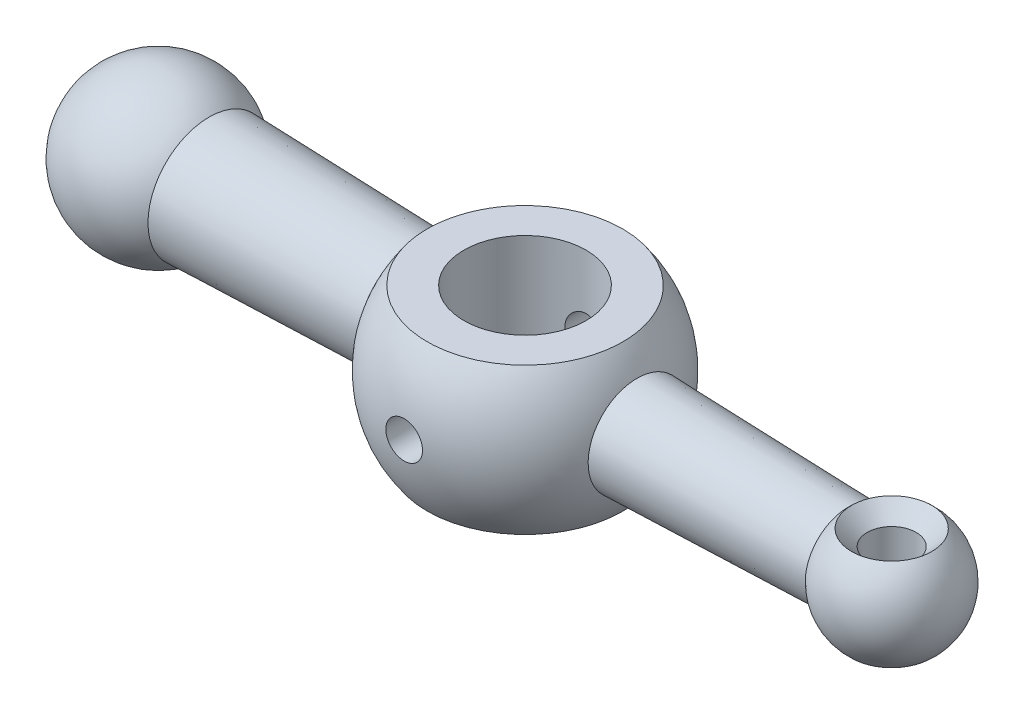
SolidWorks part; units mm, degrees
ref_plane "Спереди" through (0, 0, 0) normal (0, 0, 1) x (1, 0, 0)
ref_plane "Сверху" through (0, 0, 0) normal (0, 1, 0) x (1, 0, 0)
ref_plane "Справа" through (0, 0, 0) normal (1, 0, 0) x (0, 0, -1)
sketch "Эскиз1" plane through (0, 0, 0) normal (0, 0, 1) x (1, 0, 0)
  line L0 (0, 0) -> (-60, 0) construction
  line L1 (0, 0) -> (60, 0) construction
  line L2 (0, 0) -> (0, 5.8099) construction
  line L3 (-51.6934, 10) -> (-17.8438, 9.0332)
  line L5 (18.3303, 8) -> (52.8718, 7.0134)
  line L7 (-73, 0) -> (70, 0)
  arc A0 (18.3303, 8) -> (-17.8438, 9.0332) centre (0, 0) ccw
  arc A1 (70, 0) -> (52.8718, 7.0134) centre (60, 0) ccw
  arc A2 (-51.6934, 10) -> (-73, 0) centre (-60, 0) ccw
  point P10 (18.3303, 8)
  dimension "D1" = 40
  dimension "D4" = 20
  dimension "D5" = 26
  dimension "D2" = 60
  dimension "D3" = 60
  dimension "D6" = 10
  dimension "D7" = 8
revolve "Повернуть1" add sketch "Эскиз1" angle 360 about L7
sketch "Эскиз2" plane through (0, 0, 0) normal (0, 0, 1) x (1, 0, 0)
  line L0 (0, -12) -> (0, 12)
  line L1 (10, 12) -> (16, 12)
  line L2 (-73, 0) -> (70, 0) construction
  line L3 (70, 0) -> (64, 0) construction
  line L4 (10, -12) -> (16, -12)
  line L5 (10, 12) -> (10, -12)
  line L6 (0, 12) -> (0, 20)
  line L7 (0, -12) -> (0, -20)
  line L8 (0, 0) -> (0, 34.8855) construction
  line L15 (60, -15.2723) -> (60, 15.2723)
  line L16 (64, -8) -> (64, 8)
  line L17 (64, 8) -> (66, 8)
  line L18 (66, 8) -> (66, 15.2723)
  line L19 (66, 15.2723) -> (60, 15.2723)
  line L20 (66, -15.2723) -> (60, -15.2723)
  line L21 (64, -8) -> (66, -8)
  line L22 (60, 0) -> (-73, 0) construction
  line L23 (66, -8) -> (66, -15.2723)
  arc A0 (18.3303, 8) -> (-17.8438, 9.0332) centre (0, 0) ccw construction
  arc A1 (0, -20) -> (16, -12) centre (0, 0) ccw
  arc A3 (16, 12) -> (0, 20) centre (0, 0) ccw
  arc A4 (70, 0) -> (52.8718, 7.0134) centre (60, 0) ccw construction
  point P34 (64, 0)
  point P35 (60, 0)
  dimension "D2" = 10
  dimension "D1" = 12
  dimension "D3" = 4
  dimension "D4" = 8
revolve "Вырез-Повернуть1" cut sketch "Эскиз2" angle 360 about L8
revolve "Вырез-Повернуть2" cut sketch "Эскиз2<3>" angle 360 about L15 region at (62.5769, 0, 0)
sketch "Эскиз2<3>" plane through (0, 0, 0) normal (0, 0, 1) x (1, 0, 0) same geometry as "Эскиз2"
chamfer "Фаска1" distance 3 angle 45 2 edges at (64, -8, 0) (64, 8, 0)
sketch "Эскиз3" plane through (0, 0, 0) normal (0, 0, 1) x (1, 0, 0)
  circle A0 centre (0, 0) radius 3
  dimension "D1" = 6
extrude "Вырез-Вытянуть1" cut sketch "Эскиз3" against normal mid plane 100
